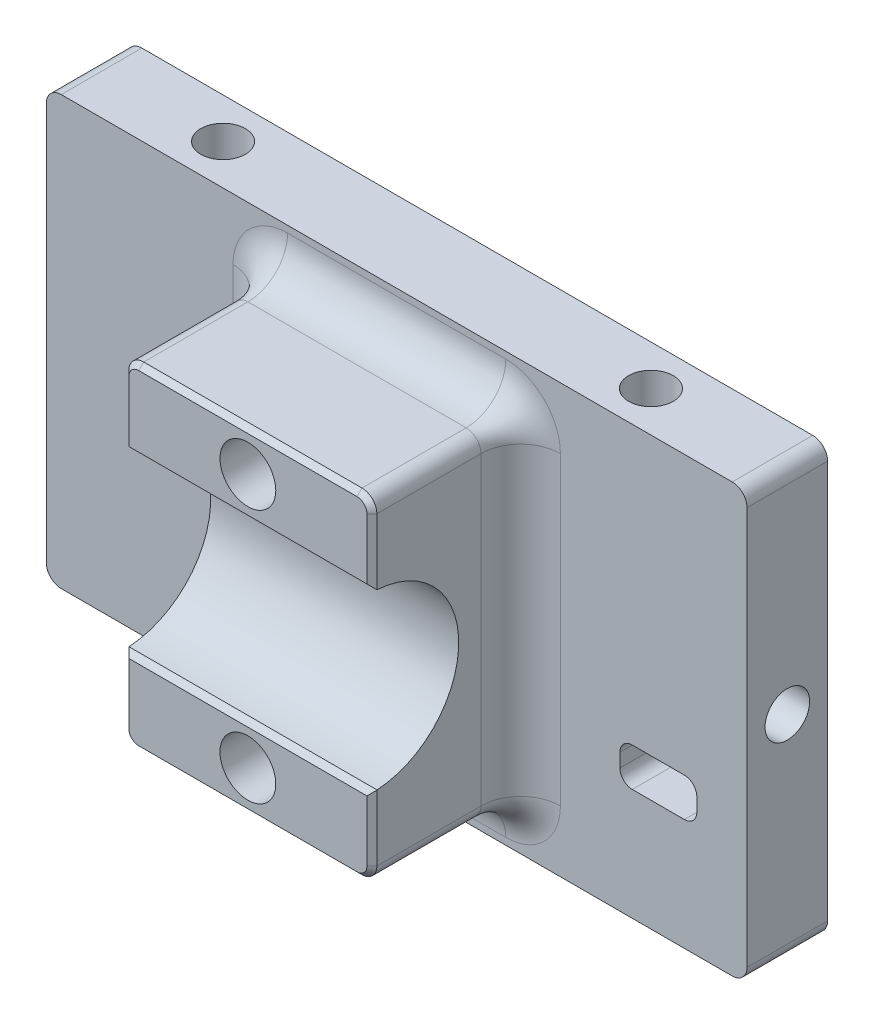
SolidWorks part; units mm, degrees
ref_plane "Plan de face" through (0, 0, 0) normal (0, 0, 1) x (1, 0, 0)
ref_plane "Plan de dessus" through (0, 0, 0) normal (0, 1, 0) x (1, 0, 0)
ref_plane "Plan de droite" through (0, 0, 0) normal (1, 0, 0) x (0, 0, -1)
sketch "Esquisse1" plane through (0, 0, 0) normal (0, 0, 1) x (1, 0, 0)
  line L1 (28.25, 17.25) -> (-28.25, 17.25)
  line L2 (28.25, 17.25) -> (28.25, -17.25)
  line L3 (28.25, -17.25) -> (-28.25, -17.25)
  line L4 (-28.25, 17.25) -> (-28.25, -17.25)
  line L5 (28.25, 17.25) -> (-28.25, -17.25) construction
  line L6 (28.25, -17.25) -> (-28.25, 17.25) construction
  point P0 (0, 0)
  dimension "D1" = 56.5
  dimension "D2" = 34.5
extrude "Base" add sketch "Esquisse1" along normal blind 6.5
sketch "Esquisse2" plane through (-28.25, 0, 0) normal (-1, 0, 0) x (0, 0, 1)
  line L0 (6.5, -17.25) -> (0, -17.25) construction
  circle A0 centre (3.25, 0) radius 1.8
  point P5 (3.25, -17.25)
  dimension "D1" = 3.6
sketch "Esquisse3" plane through (28.25, 0, 0) normal (1, 0, 0) x (0, 0, -1)
  circle A0 centre (-3.25, 0) radius 1.8
  circle A1 centre (-3.25, 0) radius 1.8 construction
extrude "Insert_M3_L" cut sketch "Esquisse2" against normal blind 3.2 contours A0
extrude "Insert_M3_R" cut sketch "Esquisse3" against normal blind 3.2
sketch "Esquisse4" plane through (0, 17.25, 0) normal (0, 1, 0) x (1, 0, 0)
  line L0 (-28.25, -6.5) -> (-28.25, 0) construction
  line L1 (28.25, -6.5) -> (28.25, 0) construction
  circle A0 centre (-17.25, -3.25) radius 1.8
  circle A1 centre (17.25, -3.25) radius 1.8
  point P9 (-28.25, -3.25)
  dimension "D3" = 3.6
  dimension "D1" = 11
  dimension "D2" = 11
sketch "Esquisse5" plane through (0, -17.25, -17) normal (0, 1, 0) x (1, 0, 0)
  circle A0 centre (-17.25, -20.25) radius 1.8
  circle A1 centre (17.25, -20.25) radius 1.8
  dimension "D3" = 3.6
extrude "Insert_M3_TOP" cut sketch "Esquisse4" against normal blind 3.2
extrude "Insert_M3_BOT" cut sketch "Esquisse5" along normal blind 3.2
sketch "Esquisse11" plane through (-25.05, 0, 0) normal (-1, 0, 0) x (0, 0, 1)
  circle A0 centre (3.25, 0) radius 1.1
  dimension "D1" = 2.2
extrude "Passage_Vis_L" cut sketch "Esquisse11" against normal blind 5
sketch "Esquisse12" plane through (25.05, 0, 0) normal (1, 0, 0) x (0, 0, -1)
  circle A0 centre (-3.25, 0) radius 1.1
  dimension "D1" = 2.2
extrude "Passage_Vis_R" cut sketch "Esquisse12" against normal blind 5
sketch "Esquisse10" plane through (0, 14.05, 0) normal (0, 1, 0) x (1, 0, 0)
  circle A0 centre (-17.25, -3.25) radius 1.1
  circle A1 centre (17.25, -3.25) radius 1.1
  dimension "D1" = 2.2
extrude "Passage_Vis_TOP" cut sketch "Esquisse10" against normal blind 5
sketch "Esquisse13" plane through (0, -14.05, 0) normal (0, -1, 0) x (1, 0, 0)
  circle A0 centre (-17.25, 3.25) radius 1.1
  circle A1 centre (17.25, 3.25) radius 1.1
  dimension "D1" = 2.2
extrude "Passage_Vis_BOT" cut sketch "Esquisse13" against normal blind 5
fillet "Congé1" radius 1.2 4 edges at (-28.25, -17.25, 3.25) (28.25, -17.25, 3.25) (28.25, 17.25, 3.25) (-28.25, 17.25, 3.25)
chamfer "Chanfrein1" [suppressed] distance 1 angle 45
sketch "Esquisse6" plane through (0, 0, 6.5) normal (0, 0, 1) x (1, 0, 0)
  line L1 (10, 13.5) -> (-10, 13.5)
  line L2 (10, 13.5) -> (10, -13.5)
  line L3 (10, -13.5) -> (-10, -13.5)
  line L4 (-10, 13.5) -> (-10, -13.5)
  line L5 (10, 13.5) -> (-10, -13.5) construction
  line L6 (10, -13.5) -> (-10, 13.5) construction
  point P0 (0, 0)
  dimension "D1" = 20
  dimension "D2" = 27
extrude "Support_Fixation" add sketch "Esquisse6" along normal blind 12
sketch "Esquisse7" plane through (-10, 0, 0) normal (-1, 0, 0) x (0, 0, 1)
  line L0 (18.5, 13.5) -> (18.5, -13.5) construction
  line L1 (18.5, 7) -> (18.5, -7)
  arc A0 (18.5, 7) -> (18.5, -7) centre (18.5, 0) ccw
  dimension "D1" = 7
extrude "Passage_Guidon" cut sketch "Esquisse7" against normal up to next
fillet "Congé_Vertical" radius 1.2 4 edges at (-10, 13.5, 12.5) (10, 13.5, 12.5) (10, -13.5, 12.5) (-10, -13.5, 12.5)
fillet "Congé_Base" radius 3.2 8 edges at (-9.6485, -13.1485, 6.5) (-10, 0, 6.5) (-9.6485, 13.1485, 6.5) (0, 13.5, 6.5) (9.6485, 13.1485, 6.5) (10, 0, 6.5) (9.6485, -13.1485, 6.5) (0, -13.5, 6.5)
sketch "Esquisse8" plane through (0, 0, 18.5) normal (0, 0, 1) x (1, 0, 0)
  line L1 (10, 7) -> (-10, 7) construction
  line L2 (10.175, 0) -> (-10.175, 0) construction
  line L3 (8.8, 13.5) -> (-8.8, 13.5) construction
  circle A0 centre (0, 10.25) radius 2.25
  circle A1 centre (0, -10.25) radius 2.25
  point P17 (0, 13.5)
  dimension "D1" = 4.5
  dimension "D2" = 3.25
extrude "Inserts_M3_Fixation" cut sketch "Esquisse8" against normal blind 3.2
chamfer "Chanfrein_Fixation" distance 0.4 angle 45 12 edges at (0, -7, 18.5) (0, 7, 18.5) (-10, -9.65, 18.5) (10, -9.65, 18.5) (-9.6485, -13.1485, 18.5) (9.6485, -13.1485, 18.5) (0, -13.5, 18.5) (10, 9.65, 18.5) (-10, 9.65, 18.5) (9.6485, 13.1485, 18.5) (-9.6485, 13.1485, 18.5) (0, 13.5, 18.5)
sketch "Esquisse9" plane through (0, 0, 15.3) normal (0, 0, 1) x (1, 0, 0)
  line L0 (10.175, 0) -> (-10.175, 0) construction
  circle A0 centre (0, 10.25) radius 1.6
  circle A1 centre (0, -10.25) radius 1.6
  dimension "D1" = 3.2
extrude "Passage_Vis_M3" cut sketch "Esquisse9" against normal blind 5
sketch "Esquisse14" plane through (0, 0, 6.5) normal (0, 0, 1) x (1, 0, 0)
  line L0 (-27.05, -17.25) -> (27.05, -17.25) construction
  line L1 (19, -5.15) -> (23.2, -5.15)
  line L2 (18, -6.15) -> (18, -7.25)
  line L3 (19, -8.25) -> (23.2, -8.25)
  line L4 (24.2, -6.15) -> (24.2, -7.25)
  line L5 (10, -12.3) -> (10, 12.3) construction
  arc A2 (23.2, -5.15) -> (24.2, -6.15) centre (23.2, -6.15) cw
  arc A3 (23.2, -8.25) -> (24.2, -7.25) centre (23.2, -7.25) ccw
  arc A4 (18, -7.25) -> (19, -8.25) centre (19, -7.25) ccw
  arc A5 (19, -5.15) -> (18, -6.15) centre (19, -6.15) ccw
  point P10 (24.2, -5.15)
  point P13 (24.2, -8.25)
  point P18 (18, -5.15)
  dimension "D5" = 1
  dimension "D1" = 6.2
  dimension "D2" = 3.1
  dimension "D3" = 9
  dimension "D4" = 8
extrude "Passe_Cable" cut sketch "Esquisse14" against normal blind 8 contours L4 L1 L2 L3 region at (21.1, -6.7, 6.5)
